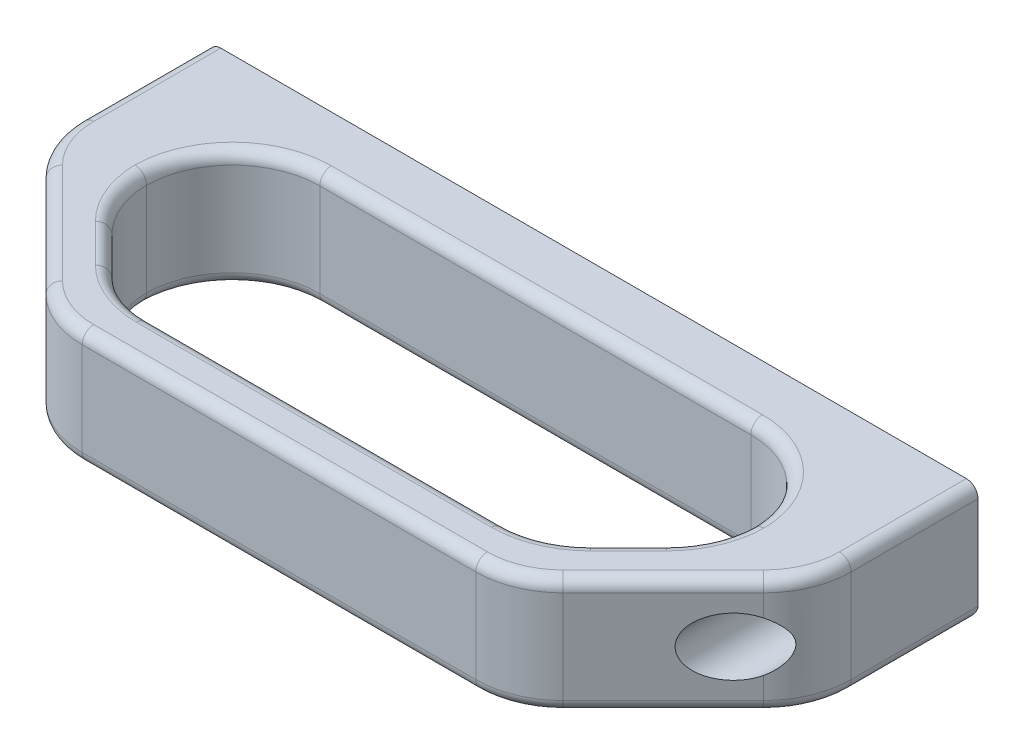
SolidWorks part; units mm, degrees
ref_plane "Front Plane" through (0, 0, 0) normal (0, 0, 1) x (1, 0, 0)
ref_plane "Top Plane" through (0, 0, 0) normal (0, 1, 0) x (1, 0, 0)
ref_plane "Right Plane" through (0, 0, 0) normal (1, 0, 0) x (0, 0, -1)
ref_plane "Plane1" through (0, 20, 0) normal (0, 1, 0) x (1, 0, 0)
sketch "Sketch1" plane through (0, 20, 0) normal (0, 1, 0) x (1, 0, 0)
  line L0 (126, -28) -> (126, 0)
  line L1 (126, 0) -> (-6, 0)
  line L2 (-6, 0) -> (-6, -28)
  line L3 (-6, -28) -> (20, -54)
  line L4 (20, -54) -> (100, -54)
  line L5 (100, -54) -> (126, -28)
extrude "Boss-Extrude1" add sketch "Sketch1" against normal blind 20
sketch "Sketch2" plane through (0, 0, 0) normal (0, -1, 0) x (1, 0, 0)
  line L0 (8, 10) -> (112, 10)
  line L1 (112, 10) -> (112, 30.6863)
  line L2 (112, 30.6863) -> (96.6863, 46)
  line L3 (96.6863, 46) -> (23.3137, 46)
  line L4 (23.3137, 46) -> (8, 30.6863)
  line L5 (8, 30.6863) -> (8, 10)
extrude "Cut-Extrude1" cut sketch "Sketch2" against normal through all
sketch "Sketch3" plane through (0, 0, 0) normal (0, 0, -1) x (-1, 0, 0)
  line L0 (-40, 15) -> (-80, 15)
  line L1 (-80, 5) -> (-40, 5)
  arc A0 (-80, 15) -> (-80, 5) centre (-80, 10) ccw
  arc A1 (-40, 5) -> (-40, 15) centre (-40, 10) ccw
extrude "Cut-Extrude2" cut sketch "Sketch3" against normal blind 6
ref_plane "Plane2" through (0, 0, 40) normal (0, 0, 1) x (1, 0, 0)
hole_wizard "Hole1" positions "Sketch5" profile "Sketch4" legacy
sketch "Sketch5" plane through (0, 0, 40) normal (0, 0, 1) x (1, 0, 0)
  point P0 (1, 10)
  point P1 (119, 10)
sketch "Sketch4" plane through (1, 10, 40) normal (1, 0, 0) x (0, -1, 0)
  line L0 (0, 0) -> (0, 40)
  line L1 (0, 40) -> (2.5, 40)
  line L2 (2.5, 40) -> (2.5, 31)
  line L3 (2.5, 31) -> (5, 31)
  line L4 (5, 31) -> (5, 0)
  line L5 (5, 0) -> (0, 0)
  line L6 (0, 110) -> (0, -10) construction
  dimension "Diameter" = 5
  dimension "Depth" = 40
  dimension "C-Bore Diameter" = 10
  dimension "C-Bore Depth" = 31
fillet "Fillet1" radius 15 10 edges at (112, 10, 30.6863) (8, 10, 30.6863) (23.3137, 10, 46) (-6, 10, 28) (96.6863, 10, 46) (20, 10, 54) (126, 10, 28) (100, 10, 54) (8, 10, 10) (112, 10, 10) tangent propagation no
fillet "Fillet2" radius 2 39 edges at (60, 20, 10) (110.8072, 20, 30.3348) (9.1928, 20, 30.3348) (104.3431, 20, 38.3431) (15.6569, 20, 38.3431) (96.2133, 20, 44.8582) (23.7867, 20, 44.8582) (60, 20, 46) (60, 0, 10) (110.8072, 0, 30.3348) (104.3431, 0, 38.3431) (96.2133, 0, 44.8582) (60, 0, 46) (23.7867, 0, 44.8582) (15.6569, 0, 38.3431) (9.1928, 0, 30.3348) (-6, 20, 10.8934) (-4.8582, 20, 27.527) (7, 20, 41) (20.473, 20, 52.8582) (60, 20, 54) (99.527, 20, 52.8582) (113, 20, 41) (126, 20, 10.8934) (124.8582, 20, 27.527) (-6, 0, 10.8934) (-4.8582, 0, 27.527) (7, 0, 41) (20.473, 0, 52.8582) (60, 0, 54) (99.527, 0, 52.8582) (113, 0, 41) (124.8582, 0, 27.527) (126, 0, 10.8934) (60, 0, 0) (107.513, 0, 14.3007) (12.487, 0, 14.3007) (12.487, 20, 14.3007) (107.513, 20, 14.3007) tangent propagation no
